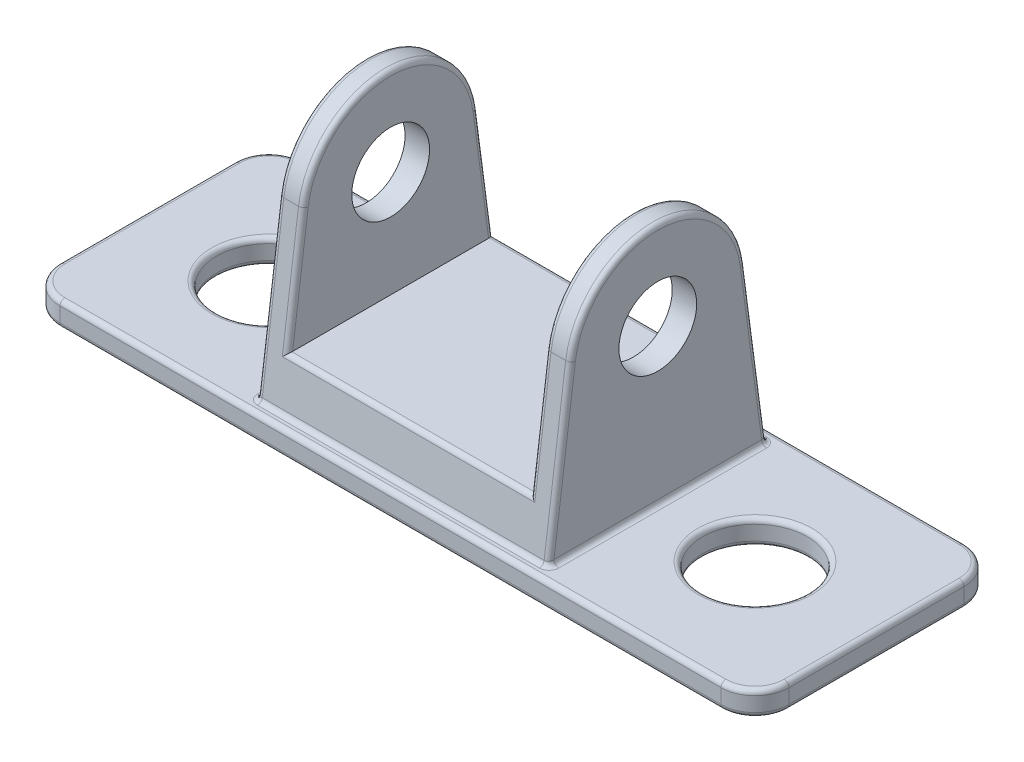
SolidWorks part; units mm, degrees
ref_plane "Front Plane" through (0, 0, 0) normal (0, 0, 1) x (1, 0, 0)
ref_plane "Top Plane" through (0, 0, 0) normal (0, 1, 0) x (1, 0, 0)
ref_plane "Right Plane" through (0, 0, 0) normal (1, 0, 0) x (0, 0, -1)
sketch "Sketch2" plane through (0, 0, 0) normal (0, 1, 0) x (1, 0, 0)
  line L0 (0, 25) -> (0, -25) construction
  line L1 (-68, 25) -> (68, 25)
  line L2 (-75, 18) -> (-75, -18)
  line L3 (-68, -25) -> (68, -25)
  line L4 (75, 18) -> (75, -18)
  arc A0 (-75, -18) -> (-68, -25) centre (-68, -18) ccw
  arc A1 (68, -25) -> (75, -18) centre (68, -18) ccw
  arc A2 (68, 25) -> (75, 18) centre (68, 18) cw
  arc A3 (-68, 25) -> (-75, 18) centre (-68, 18) ccw
  point P0 (0, 0)
  point P8 (0, 0)
  point P9 (-91.495, 33.241)
  dimension "D1" = 7
extrude "Boss-Extrude1" add sketch "Sketch2" along normal blind 5
sketch "Sketch3" plane through (0, 5, 0) normal (0, 1, 0) x (1, 0, 0)
  line L0 (2.1575, 22.5) -> (2.1575, 25) construction
  line L1 (-30, 22.5) -> (30, 22.5)
  line L2 (-30, 22.5) -> (-30, -22.5)
  line L3 (-30, -22.5) -> (30, -22.5)
  line L4 (30, 22.5) -> (30, -22.5)
  line L5 (68, 25) -> (-68, 25) construction
  line L6 (8.1985, -22.5) -> (8.1985, -25) construction
  line L7 (-68, -25) -> (68, -25) construction
  line L8 (-75, 5.1953) -> (-30, 5.1953) construction
  line L9 (-75, 18) -> (-75, -18) construction
  line L10 (30, 5.1953) -> (75, 5.1953) construction
  line L11 (75, -18) -> (75, 18) construction
  point P0 (0, 0)
  point P22 (27.7384, 23.231)
extrude "Boss-Extrude2" add sketch "Sketch3" along normal blind 50
sketch "Sketch4" plane through (30, 0, 0) normal (1, 0, 0) x (0, 0, -1)
  line L0 (0, 55) -> (0, 5) construction
  line L3 (-22.5, 5) -> (-17.9566, 39.267)
  line L4 (22.5, 5) -> (17.9566, 39.267)
  line L5 (-22.5, 5) -> (-22.5, 55)
  line L6 (-22.5, 55) -> (22.5, 55)
  line L7 (22.5, 55) -> (22.5, 5)
  arc A1 (17.9566, 39.267) -> (-17.9566, 39.267) centre (0, 36.8862) ccw
  line M3 (22.5, 5) -> (22.5, 55)
  line M4 (22.5, 55) -> (-22.5, 55)
  line M5 (-22.5, 55) -> (-22.5, 5)
extrude "Cut-Extrude1" cut sketch "Sketch4" against normal blind 86 contours A1 L4 M3 M4 | A1 L6 L3 M5 region at (30, 41.4623, 18.5283) region at (30, 41.4623, -18.5283)
sketch "Sketch5" plane through (0, 0, -25) normal (0, 0, -1) x (-1, 0, 0)
  line L0 (30, 39.267) -> (-30, 39.267) construction
  line L1 (-24.9711, 63.5341) -> (24.9711, 63.5341)
  line L2 (-24.9711, 63.5341) -> (-24.9711, 15)
  line L3 (-24.9711, 15) -> (24.9711, 15)
  line L4 (24.9711, 63.5341) -> (24.9711, 15)
  line L5 (-24.9711, 63.5341) -> (24.9711, 15) construction
  line L6 (-24.9711, 15) -> (24.9711, 63.5341) construction
  line L7 (-11.3598, 15) -> (-11.3598, 5)
  line L8 (-30, 5) -> (30, 5) construction
  point P0 (0, 39.267)
extrude "Cut-Extrude2" cut sketch "Sketch5" against normal blind 86 contours L4 L1 L2 L3 region at (0, 39.267, -25)
sketch "Sketch6" plane through (-30, 0, 0) normal (-1, 0, 0) x (0, 0, 1)
  circle A0 centre (0, 36.8862) radius 8
extrude "Cut-Extrude3" cut sketch "Sketch6" against normal blind 86
sketch "Sketch8" plane through (0, 5, 0) normal (0, 1, 0) x (1, 0, 0)
  line L0 (-50, 25) -> (-50, -25) construction
  line L1 (68, 25) -> (-68, 25) construction
  line L2 (-68, -25) -> (68, -25) construction
  line L3 (-50, 0) -> (-75, 0) construction
  line L4 (-75, 18) -> (-75, -18) construction
  line L5 (-65.9113, 0) -> (-65.9113, 25) construction
  circle A0 centre (-50, 0) radius 10.7811
extrude "Cut-Extrude4" cut sketch "Sketch8" against normal blind 86
ref_plane "Plane1" through (0, 0, 0) normal (1, 0, 0) x (0, 0, -1)
mirror "Mirror1" about plane through (0, 0, 0) normal (1, 0, 0) of "Cut-Extrude4"
fillet "Fillet1" radius 1 38 edges at (0, 5, 22.5) (-30, 5, 0) (30, 5, 0) (-30, 22.1335, 20.2283) (-24.9711, 27.1335, 19.5654) (24.9711, 27.1335, 19.5654) (30, 22.1335, 20.2283) (-72.9497, 0, 22.9497) (-75, 0, 0) (-72.9497, 0, -22.9497) (0, 0, -25) (72.9497, 0, -22.9497) (75, 0, 0) (72.9497, 0, 22.9497) (-72.9497, 5, 22.9497) (-75, 5, 0) (-72.9497, 5, -22.9497) (0, 5, -25) (72.9497, 5, -22.9497) (75, 5, 0) (72.9497, 5, 22.9497) (-30, 22.1335, -20.2283) (0, 5, -22.5) (30, 22.1335, -20.2283) (24.9711, 27.1335, -19.5654) (0, 15, -21.1741) (-24.9711, 27.1335, -19.5654) (-30, 55, 0) (-24.9711, 55, 0) (24.9711, 55, 0) (30, 55, 0) (-50, 5, 10.7811) (-50, 0, 10.7811) (50, 0, 10.7811) (50, 5, 10.7811) (0, 15, 21.1741) (0, 0, 25) (0, 5, 25)
